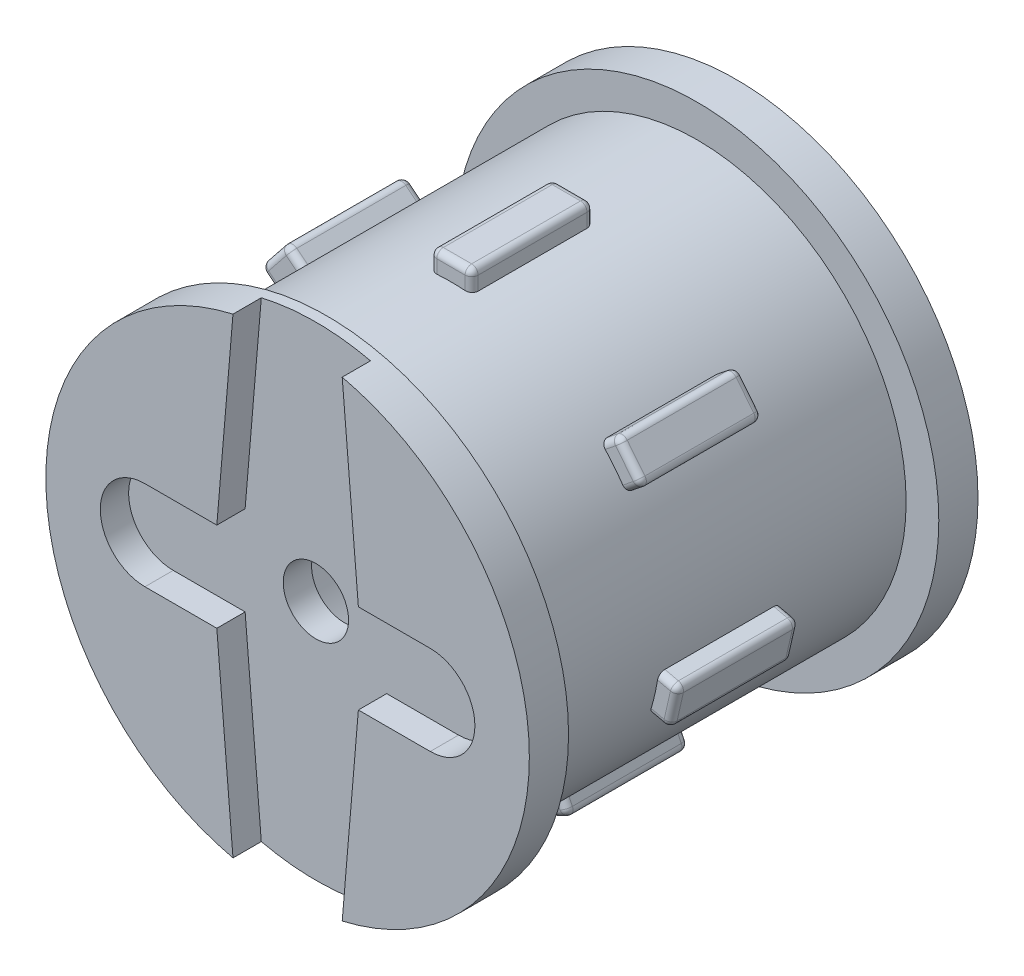
SolidWorks part; units mm, degrees
ref_plane "Ebene vorne" through (0, 0, 0) normal (0, 0, 1) x (1, 0, 0)
ref_plane "Ebene oben" through (0, 0, 0) normal (0, 1, 0) x (1, 0, 0)
ref_plane "Ebene rechts" through (0, 0, 0) normal (1, 0, 0) x (0, 0, -1)
sketch "Skizze1" plane through (0, 0, 0) normal (0, 0, 1) x (1, 0, 0)
  circle A0 centre (0, 0) radius 9.6
  dimension "D1" = 19.2
extrude "Aufsatz-Linear austragen1" add sketch "Skizze1" along normal blind 10.3 and the other way blind 10.3
ref_axis "Rotationsachse" through (0, 0, -10.3) along (0, 0, 1)
sketch "Skizze2" plane through (0, 0, 10.3) normal (0, 0, 1) x (1, 0, 0)
  circle A0 centre (0, 0) radius 11.1
  dimension "D1" = 22.2
extrude "Aufsatz-Linear austragen2" add sketch "Skizze2" against normal blind 1.8
sketch "Skizze3" plane through (0, 0, -10.3) normal (0, 0, -1) x (-1, 0, 0)
  circle A0 centre (0, 0) radius 11.1
  dimension "D1" = 22.2
extrude "Aufsatz-Linear austragen3" add sketch "Skizze3" against normal blind 1.8
sketch "Skizze12" plane through (0, 0, 10.3) normal (0, 0, 1) x (1, 0, 0)
  line L0 (3.25, -2.05) -> (2, -16.8)
  line L1 (-3.05, 2.05) -> (3.05, 2.05)
  line L2 (-3.05, 2.05) -> (-3.05, -2.05)
  line L3 (-3.05, -2.05) -> (3.05, -2.05)
  line L4 (3.05, 2.05) -> (3.05, -2.05)
  line L5 (-3.05, 2.05) -> (3.05, -2.05) construction
  line L6 (-3.05, -2.05) -> (3.05, 2.05) construction
  line L7 (3.05, 2.05) -> (6.55, 2.05)
  line L8 (3.05, 2.05) -> (3.05, -2.05)
  line L9 (3.05, -2.05) -> (6.55, -2.05)
  line L10 (6.55, 2.05) -> (6.55, -2.05)
  line L11 (-3.05, -2.05) -> (-3.25, -2.05)
  line L12 (-3.25, -2.05) -> (-2, -16.8)
  circle A0 centre (6.55, 0) radius 2.05
  circle A1 centre (0, -16.8) radius 2
  point P0 (0, 0)
  point P12 (0, -2.05)
  circle M11 centre (0, 0) radius 11.1
  dimension "D5" = 4
  dimension "D1" = 6.1
  dimension "D2" = 4.1
  dimension "D3" = 3.5
  dimension "D4" = 14.75
  dimension "D6" = 3.05
  dimension "D7" = 3.25
  dimension "D8" = 3.25
extrude "Schnitt-Linear austragen1" cut sketch "Skizze12" against normal blind 1.3 contours A1 | A1 L0 L12 M11 | L11 L12 L0 L9 L3 M11 | L4 L1 L2 L3 | A0 L7 L4 L9 | L10 A0 | L10 A0 region at (0, -6.3308, 10.3) region at (4.0504, 0, 10.3) region at (0, -13.1106, 10.3) region at (0, 0, 10.3) region at (5.68, 0, 10.3) region at (7.42, 0, 10.3) region at (0, -16.8, 10.3)
sketch "Skizze8" plane through (0, 0, 0) normal (1, 0, 0) x (0, 0, -1)
  line L0 (10.3, 0) -> (10.3, 8)
  line L1 (10.3, -11.1) -> (10.3, 11.1) construction
  line L2 (10.3, 8) -> (8.5, 8)
  line L3 (8.5, 11.1) -> (8.5, -11.1) construction
  line L4 (8.5, 8) -> (-7.7, 3.5)
  line L6 (-7.7, 3.5) -> (-7.7, 0)
  line L7 (-7.7, 0) -> (10.3, 0)
  dimension "D1" = 8
  dimension "D2" = 3.5
  dimension "D3" = 18
revolve "Schnitt-Rotation1" cut sketch "Skizze8" angle 360 about axis through (0, 0, -10.3) along (0, 0, 1)
ref_plane "Schnittebene_Zaehne" through (0, 0, 0) normal (0, 0, -1) x (-1, 0, 0)
sketch "Skizze11" plane through (0, 0, 0) normal (0, 0, -1) x (-1, 0, 0)
  line L0 (0, 0) -> (0, 12.664) construction
  line L6 (-0.95, 8.71) -> (0.95, 8.71)
  line L7 (-0.95, 8.71) -> (-0.95, 10.49)
  line L8 (-0.95, 10.49) -> (0.95, 10.49)
  line L9 (0.95, 8.71) -> (0.95, 10.49)
  line L10 (-0.95, 8.71) -> (0.95, 10.49) construction
  line L11 (-0.95, 10.49) -> (0.95, 8.71) construction
  circle A1 centre (0, 0) radius 9.6 construction
  point P3 (0, 9.6)
  dimension "D1" = 0.89
  dimension "D2" = 1.9
extrude "Aufsatz-Linear austragen4" add sketch "Skizze11" along normal blind 2.8 and the other way blind 2.8
pattern_circular "Kreismuster2" count 7 over 360 about axis through (0, 0, -10.3) along (0, 0, 1) of "Aufsatz-Linear austragen4"
fillet "Verrundung1" radius 0.3 56 edges at (8.2014, 6.5404, 2.8) (7.6091, 7.2831, 0) (8.2014, 6.5404, -2.8) (8.7937, 5.7977, 0) (-8.4274, 5.5055, 2.8) (-7.2428, 6.991, 2.8) (-7.2428, 6.991, -2.8) (-8.4274, 5.5055, -2.8) (-9.5588, -3.1562, -2.8) (-9.9816, -1.3038, -2.8) (-9.5588, -3.1562, 2.8) (-9.9816, -1.3038, 2.8) (-5.2041, -8.6168, -2.8) (-3.4922, -9.4412, -2.8) (-3.4922, -9.4412, 2.8) (-5.2041, -8.6168, 2.8) (5.2041, -8.6168, 2.8) (3.4922, -9.4412, 2.8) (3.4922, -9.4412, -2.8) (5.2041, -8.6168, -2.8) (9.5588, -3.1562, 2.8) (9.5588, -3.1562, -2.8) (9.9816, -1.3038, 2.8) (9.9816, -1.3038, -2.8) (8.4274, 5.5055, 2.8) (8.4274, 5.5055, -2.8) (7.2428, 6.991, -2.8) (7.2428, 6.991, 2.8) (0.95, 10.0214, 2.8) (0.95, 10.0214, -2.8) (-0.95, 10.0214, -2.8) (-0.95, 10.0214, 2.8) (10.4384, -1.4081, 0) (10.227, -2.3342, 2.8) (10.227, -2.3342, -2.8) (10.0156, -3.2604, 0) (4.5514, -9.4512, 2.8) (4.5514, -9.4512, -2.8) (5.4074, -9.039, 0) (3.6955, -9.8634, 0) (-4.5514, -9.4512, 2.8) (-4.5514, -9.4512, -2.8) (-5.4074, -9.039, 0) (-3.6955, -9.8634, 0) (-10.227, -2.3342, 2.8) (-10.227, -2.3342, -2.8) (-10.0156, -3.2604, 0) (-10.4384, -1.4081, 0) (-8.2014, 6.5404, -2.8) (-8.2014, 6.5404, 2.8) (-8.7937, 5.7977, 0) (-7.6091, 7.2831, 0) (0, 10.49, -2.8) (0, 10.49, 2.8) (0.95, 10.49, 0) (-0.95, 10.49, 0)
pattern_circular "Kreismuster3" count 2 over 360 about axis through (0, 0, -10.3) along (0, 0, 1) of "Schnitt-Linear austragen1"
sketch "Skizze14" plane through (0, 0, 10.3) normal (0, 0, 1) x (1, 0, 0)
  circle A0 centre (0, 0) radius 1.5
  dimension "D1" = 3
extrude "Schnitt-Linear austragen2" cut sketch "Skizze14" against normal up to surface (2.6 mm away) up to face at (-3.5, 0, 7.7)
